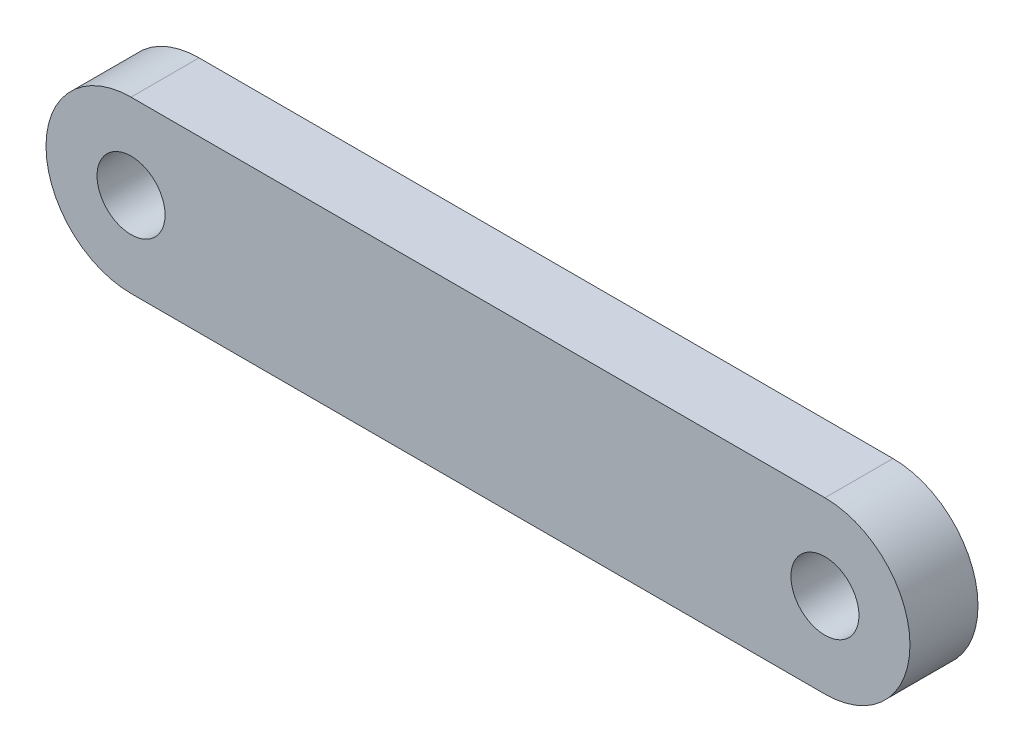
SolidWorks part; units mm, degrees
material "ABS"
ref_plane "Front Plane" through (0, 0, 0) normal (0, 0, 1) x (1, 0, 0)
ref_plane "Top Plane" through (0, 0, 0) normal (0, 1, 0) x (1, 0, 0)
ref_plane "Right Plane" through (0, 0, 0) normal (1, 0, 0) x (0, 0, -1)
sketch "Sketch1" plane through (0, 0, 0) normal (0, 0, 1) x (1, 0, 0)
  line L0 (0, 3.175) -> (25.908, 3.175)
  line L1 (0, -3.175) -> (25.908, -3.175)
  circle A0 centre (0, 0) radius 1.27
  circle A1 centre (0, 0) radius 3.175
  circle A2 centre (25.908, 0) radius 1.27
  circle A3 centre (25.908, 0) radius 3.175
  dimension "D1" = 2.54
  dimension "D2" = 6.35
  dimension "D3" = 25.908
extrude "Boss-Extrude2" add sketch "Sketch1" along normal blind 2.54 contours A1 A0 | A3 A2 | A3 L0 A1 L1 region at (12.954, 0, 0) region at (2.1816, 2.1816, 0) region at (28.0896, 2.1816, 0)
